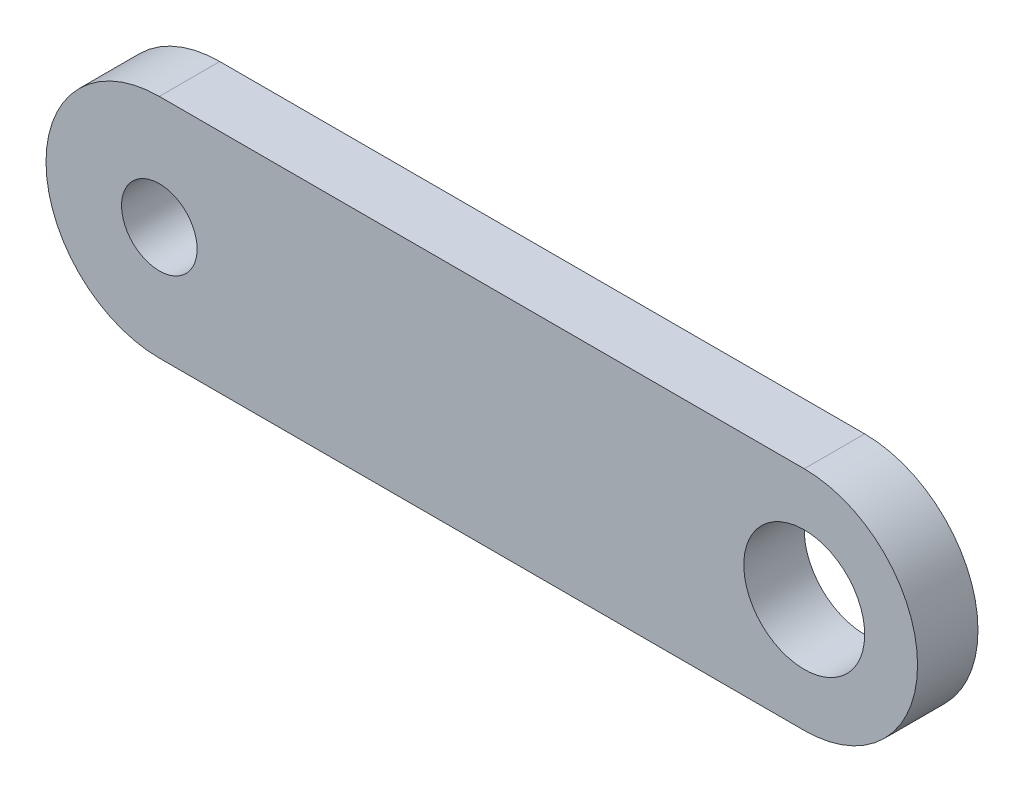
SolidWorks part; units mm, degrees
material "ABS"
ref_plane "Front Plane" through (0, 0, 0) normal (0, 0, 1) x (1, 0, 0)
ref_plane "Top Plane" through (0, 0, 0) normal (0, 1, 0) x (1, 0, 0)
ref_plane "Right Plane" through (0, 0, 0) normal (1, 0, 0) x (0, 0, -1)
sketch "Sketch1" plane through (0, 0, 0) normal (0, 0, 1) x (1, 0, 0)
  line L0 (0, 4.7625) -> (27.1018, 4.7625)
  line L1 (0, -4.7625) -> (27.1018, -4.7625)
  circle A0 centre (0, 0) radius 1.5875
  circle A1 centre (0, 0) radius 4.7625
  circle A2 centre (27.1018, 0) radius 2.54
  circle A3 centre (27.1018, 0) radius 4.7625
  dimension "D1" = 3.175
  dimension "D2" = 9.525
extrude "Boss-Extrude2" add sketch "Sketch1" along normal blind 2.54 contours A1 A0 | A3 A2 | A3 L0 A1 L1 region at (13.5509, 0, 0) region at (3.2723, 3.2723, 0) region at (30.3741, 3.2723, 0)
